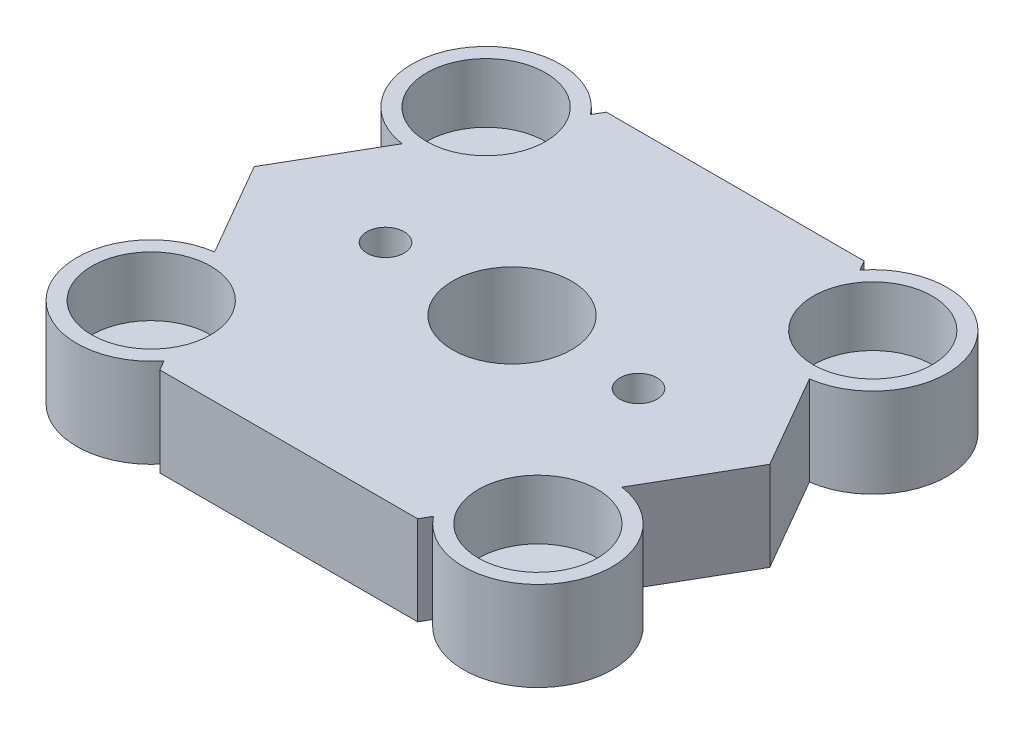
SolidWorks part; units mm, degrees
ref_plane "Front Plane" through (0, 0, 0) normal (0, 0, 1) x (1, 0, 0)
ref_plane "Top Plane" through (0, 0, 0) normal (0, 1, 0) x (1, 0, 0)
ref_plane "Right Plane" through (0, 0, 0) normal (1, 0, 0) x (0, 0, -1)
sketch "Sketch2" plane through (0, 0, 0) normal (0, 1, 0) x (1, 0, 0)
  line L0 (-8.5, 0) -> (8.5, 0) construction
  line L1 (0, 20.1846) -> (0, -20.1846) construction
  line L2 (-12.9904, 7.5) -> (-12.9904, 15) construction
  line L3 (17.3205, 0) -> (8.6603, 15)
  line L4 (8.6603, 15) -> (-8.6603, 15)
  line L5 (-8.6603, 15) -> (-17.3205, 0)
  line L6 (-17.3205, 0) -> (-8.6603, -15)
  line L7 (-8.6603, -15) -> (8.6603, -15)
  line L8 (8.6603, -15) -> (17.3205, 0)
  line L9 (-8.6603, 15) -> (-12.9904, 15) construction
  circle A0 centre (0, 0) radius 4
  circle A1 centre (8.5, 0) radius 1.25
  circle A2 centre (-8.5, 0) radius 1.25
  circle A3 centre (0, 0) radius 15 construction
  circle A4 centre (-12.9904, 11.25) radius 5
  circle A5 centre (-12.9904, 11.25) radius 1.5
  circle A6 centre (12.9904, 11.25) radius 1.5
  circle A7 centre (12.9904, 11.25) radius 5
  circle A8 centre (12.9904, -11.25) radius 1.5
  circle A9 centre (12.9904, -11.25) radius 5
  circle A10 centre (-12.9904, -11.25) radius 5
  circle A11 centre (-12.9904, -11.25) radius 1.5
  point P7 (0, 0)
  point P8 (0, 0)
  dimension "D1" = 8
  dimension "D3" = 2.5
  dimension "D4" = 2.5
  dimension "D6" = 10
  dimension "D7" = 3
  dimension "D2" = 17
  dimension "D5" = 30
extrude "Boss-Extrude1" add sketch "Sketch2" along normal blind 6 contours A4 | L3 L4 L5 L6 L7 L8 | A10 | A9 | A7 | A6 | A5 | A0 | A1 | A2 | A11 | A8
sketch "Sketch3" plane through (0, 0, 0) normal (0, -1, 0) x (1, 0, 0)
  circle A0 centre (-8.5, 0) radius 3.5
  circle A1 centre (8.5, 0) radius 3.5
  dimension "D1" = 7
  dimension "D2" = 7
extrude "Cut-Extrude3" cut sketch "Sketch3" against normal blind 3 contours A0 | A1
sketch "Sketch4" plane through (0, 6, 0) normal (0, 1, 0) x (1, 0, 0)
  circle A0 centre (-12.9904, 11.25) radius 4
  circle A1 centre (12.9904, 11.25) radius 4
  circle A2 centre (-12.9904, -11.25) radius 4
  circle A3 centre (12.9904, -11.25) radius 4
  dimension "D1" = 8
  dimension "D2" = 8
  dimension "D3" = 8
  dimension "D4" = 8
extrude "Cut-Extrude4" cut sketch "Sketch4" against normal blind 4
